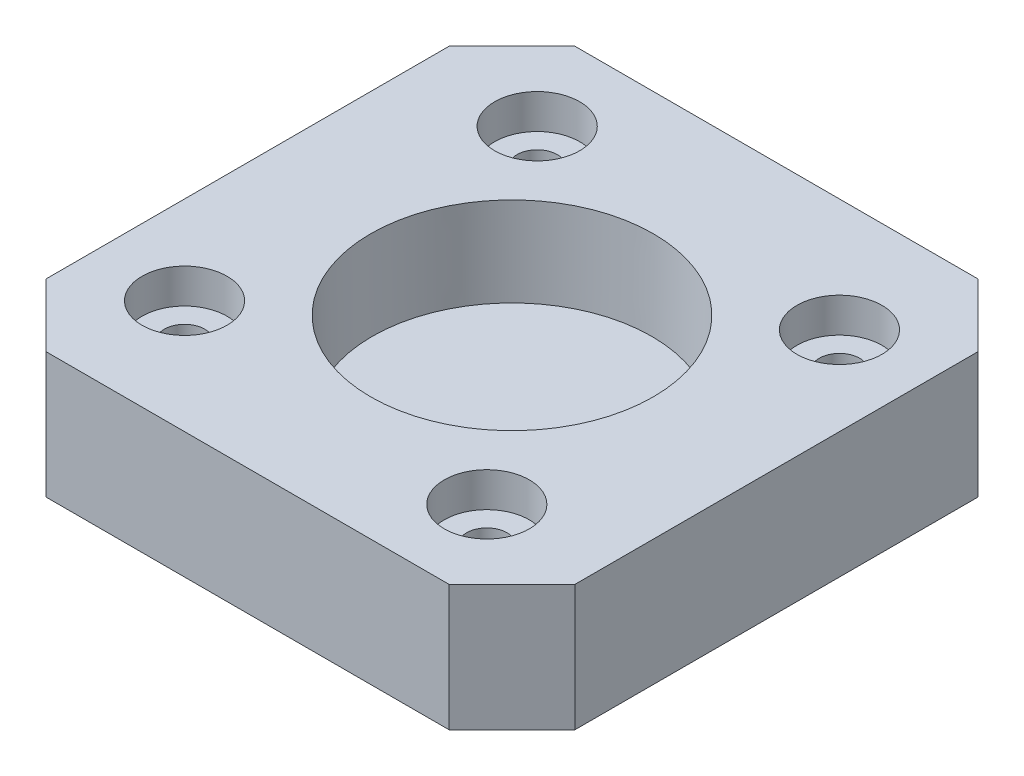
SolidWorks part; units mm, degrees
ref_plane "Front Plane" through (0, 0, 0) normal (0, 0, 1) x (1, 0, 0)
ref_plane "Top Plane" through (0, 0, 0) normal (0, 1, 0) x (1, 0, 0)
ref_plane "Right Plane" through (0, 0, 0) normal (1, 0, 0) x (0, 0, -1)
sketch "Sketch1" plane through (0, 0, 0) normal (0, 1, 0) x (1, 0, 0)
  line L1 (-21, -21) -> (21, -21)
  line L2 (-21, -21) -> (-21, 21)
  line L3 (-21, 21) -> (21, 21)
  line L4 (21, -21) -> (21, 21)
  line L5 (-21, -21) -> (21, 21) construction
  line L6 (-21, 21) -> (21, -21) construction
  point P0 (0, 0)
  dimension "D1" = 42
  dimension "D2" = 42
extrude "Boss-Extrude1" add sketch "Sketch1" along normal blind 10
sketch "Sketch2" plane through (0, 10, 0) normal (0, 1, 0) x (1, 0, 0)
  circle A0 centre (0, 0) radius 11.1
  dimension "D1" = 22.2
extrude "Cut-Extrude1" cut sketch "Sketch2" against normal blind 7
chamfer "Chamfer1" distance 7 angle 1 1 edges at (0, 10, 11.1) first distance on face at (0, 3, 11.1)
sketch "Sketch3" plane through (0, 10, 0) normal (0, 1, 0) x (1, 0, 0)
  circle A0 centre (-12, 14) radius 3.375
  circle A4 centre (14, 12) radius 3.375
  circle A5 centre (12, -14) radius 3.375
  circle A6 centre (-14, -12) radius 3.375
  point P12 (0, 0)
  point P13 (0, 0)
  dimension "D1" = 6.75
  dimension "D2" = 12
  dimension "D3" = 14
  dimension "D4" = 4
extrude "Cut-Extrude2" cut sketch "Sketch3" against normal blind 2.75
chamfer "Chamfer2" distance 5 angle 45 4 edges at (-21, 5, 21) (21, 5, 21) (21, 5, -21) (-21, 5, -21)
sketch "Sketch4" plane through (0, 7.25, 0) normal (0, 1, 0) x (1, 0, 0)
  circle A0 centre (-12, 14) radius 1.6
  circle A4 centre (-14, -12) radius 1.6
  circle A5 centre (14, 12) radius 1.6
  circle A6 centre (12, -14) radius 1.6
  dimension "D1" = 3.2
extrude "Cut-Extrude3" cut sketch "Sketch4" against normal up to next
